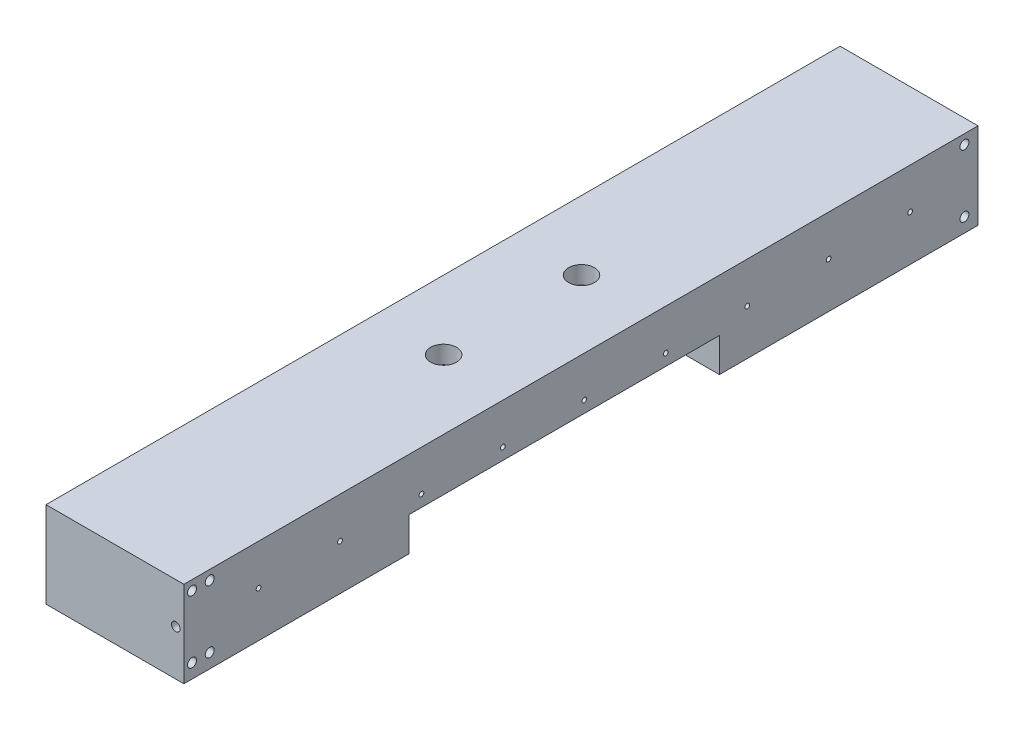
SolidWorks part; units mm, degrees
ref_plane "Front" through (0, 0, 0) normal (0, 0, 1) x (1, 0, 0)
ref_plane "Top" through (0, 0, 0) normal (0, 1, 0) x (1, 0, 0)
ref_plane "Right" through (0, 0, 0) normal (1, 0, 0) x (0, 0, -1)
sketch "Sketch1" plane through (0, 0, 0) normal (0, 0, 1) x (1, 0, 0)
  line L1 (0, 0) -> (101.6, 0)
  line L2 (0, 0) -> (0, 63.5)
  line L3 (0, 63.5) -> (101.6, 63.5)
  line L4 (101.6, 0) -> (101.6, 63.5)
  dimension "D1" = 63.5
  dimension "D2" = 101.6
extrude "Boss-Extrude1" add sketch "Sketch1" along normal blind 585.0001
sketch "Sketch2" plane through (0, 0, 0) normal (-1, 0, 0) x (0, 0, 1)
  line L0 (190.5, 0) -> (190.5, 25)
  line L1 (585.0001, 0) -> (0, 0) construction
  line L2 (190.5, 25) -> (419.1, 25)
  line L3 (419.1, 25) -> (419.1, 0)
  line L4 (419.1, 0) -> (190.5, 0)
  line L5 (0, 63.5) -> (0, 0) construction
  line L6 (393.7, 25) -> (190.5, 25) construction
  dimension "D1" = 190.5
  dimension "D3" = 228.6
extrude "Cut-Extrude1" cut sketch "Sketch2" against normal through all
sketch "Sketch5" plane through (0, 0, 0) normal (-1, 0, 0) x (0, 0, 1)
  arc A0 (6.7, 10.5) -> (13.3, 10.5) centre (10, 10.5) ccw construction
  arc A1 (13.3, 10.5) -> (6.7, 10.5) centre (10, 10.5) ccw construction
  arc A2 (6.7, 56.5) -> (13.3, 56.5) centre (10, 56.5) ccw construction
  arc A3 (13.3, 56.5) -> (6.7, 56.5) centre (10, 56.5) ccw construction
  arc A4 (6.7, 10.5) -> (13.3, 10.5) centre (10, 10.5) ccw
  arc A5 (13.3, 10.5) -> (6.7, 10.5) centre (10, 10.5) ccw
  arc A6 (6.7, 56.5) -> (13.3, 56.5) centre (10, 56.5) ccw
  arc A7 (13.3, 56.5) -> (6.7, 56.5) centre (10, 56.5) ccw
  arc A8 (170, 35.25) -> (170, 31.75) centre (170, 33.5) ccw construction
  arc A9 (170, 31.75) -> (170, 35.25) centre (170, 33.5) ccw construction
  arc A10 (110, 31.75) -> (110, 35.25) centre (110, 33.5) ccw construction
  arc A11 (110, 35.25) -> (110, 31.75) centre (110, 33.5) ccw construction
  arc A12 (50, 31.75) -> (50, 35.25) centre (50, 33.5) ccw construction
  arc A13 (50, 35.25) -> (50, 31.75) centre (50, 33.5) ccw construction
  arc A14 (170, 35.25) -> (170, 31.75) centre (170, 33.5) ccw
  arc A15 (170, 31.75) -> (170, 35.25) centre (170, 33.5) ccw
  arc A16 (110, 31.75) -> (110, 35.25) centre (110, 33.5) ccw
  arc A17 (110, 35.25) -> (110, 31.75) centre (110, 33.5) ccw
  arc A18 (50, 31.75) -> (50, 35.25) centre (50, 33.5) ccw
  arc A19 (50, 35.25) -> (50, 31.75) centre (50, 33.5) ccw
  arc A20 (530, 31.75) -> (530, 35.25) centre (530, 33.5) ccw construction
  arc A21 (530, 35.25) -> (530, 31.75) centre (530, 33.5) ccw construction
  arc A22 (470, 31.75) -> (470, 35.25) centre (470, 33.5) ccw construction
  arc A23 (470, 35.25) -> (470, 31.75) centre (470, 33.5) ccw construction
  arc A24 (410, 31.75) -> (410, 35.25) centre (410, 33.5) ccw construction
  arc A25 (410, 35.25) -> (410, 31.75) centre (410, 33.5) ccw construction
  arc A26 (350, 31.75) -> (350, 35.25) centre (350, 33.5) ccw construction
  arc A27 (350, 35.25) -> (350, 31.75) centre (350, 33.5) ccw construction
  arc A28 (290, 31.75) -> (290, 35.25) centre (290, 33.5) ccw construction
  arc A29 (290, 35.25) -> (290, 31.75) centre (290, 33.5) ccw construction
  arc A30 (230, 31.75) -> (230, 35.25) centre (230, 33.5) ccw construction
  arc A31 (230, 35.25) -> (230, 31.75) centre (230, 33.5) ccw construction
  arc A32 (530, 31.75) -> (530, 35.25) centre (530, 33.5) ccw
  arc A33 (530, 35.25) -> (530, 31.75) centre (530, 33.5) ccw
  arc A34 (470, 31.75) -> (470, 35.25) centre (470, 33.5) ccw
  arc A35 (470, 35.25) -> (470, 31.75) centre (470, 33.5) ccw
  arc A36 (410, 31.75) -> (410, 35.25) centre (410, 33.5) ccw
  arc A37 (410, 35.25) -> (410, 31.75) centre (410, 33.5) ccw
  arc A38 (350, 31.75) -> (350, 35.25) centre (350, 33.5) ccw
  arc A39 (350, 35.25) -> (350, 31.75) centre (350, 33.5) ccw
  arc A40 (290, 31.75) -> (290, 35.25) centre (290, 33.5) ccw
  arc A41 (290, 35.25) -> (290, 31.75) centre (290, 33.5) ccw
  arc A42 (230, 31.75) -> (230, 35.25) centre (230, 33.5) ccw
  arc A43 (230, 35.25) -> (230, 31.75) centre (230, 33.5) ccw
  arc A44 (582.3, 10.5) -> (575.7, 10.5) centre (579, 10.5) ccw construction
  arc A45 (575.7, 10.5) -> (582.3, 10.5) centre (579, 10.5) ccw construction
  arc A46 (562.7, 10.5) -> (569.3, 10.5) centre (566, 10.5) ccw construction
  arc A47 (569.3, 10.5) -> (562.7, 10.5) centre (566, 10.5) ccw construction
  arc A48 (575.7, 56.5) -> (582.3, 56.5) centre (579, 56.5) ccw construction
  arc A49 (582.3, 56.5) -> (575.7, 56.5) centre (579, 56.5) ccw construction
  arc A50 (562.7, 56.5) -> (569.3, 56.5) centre (566, 56.5) ccw construction
  arc A51 (569.3, 56.5) -> (562.7, 56.5) centre (566, 56.5) ccw construction
  arc A52 (582.3, 10.5) -> (575.7, 10.5) centre (579, 10.5) ccw
  arc A53 (575.7, 10.5) -> (582.3, 10.5) centre (579, 10.5) ccw
  arc A54 (562.7, 10.5) -> (569.3, 10.5) centre (566, 10.5) ccw
  arc A55 (569.3, 10.5) -> (562.7, 10.5) centre (566, 10.5) ccw
  arc A56 (575.7, 56.5) -> (582.3, 56.5) centre (579, 56.5) ccw
  arc A57 (582.3, 56.5) -> (575.7, 56.5) centre (579, 56.5) ccw
  arc A58 (562.7, 56.5) -> (569.3, 56.5) centre (566, 56.5) ccw
  arc A59 (569.3, 56.5) -> (562.7, 56.5) centre (566, 56.5) ccw
extrude "Cut-Extrude4" cut sketch "Sketch5" along normal blind 6.35 from surface contours A32 A33 | A34 A35 | A36 A37 | A38 A39 | A40 A41 | A42 A43 | A15 A14 | A16 A17 | A18 A19 starting at face at (101.6, 22.125, 298.65)
extrude "Cut-Extrude5" cut sketch "Sketch5<3>" along normal blind 25.4 from surface contours A54 A55 | A52 A53 | A56 A57 | A58 A59 | A4 A5 | A6 A7 region at (0, 10.5, 10) region at (0, 56.5, 10) region at (0, 10.5, 579) region at (0, 10.5, 566) region at (0, 56.5, 579) region at (0, 56.5, 566) starting at face at (101.6, 33.5, 531.75)
sketch "Sketch5<3>" plane through (0, 0, 0) normal (-1, 0, 0) x (0, 0, 1) same geometry as "Sketch5"
sketch "Sketch6" plane through (0, 25, 0) normal (0, -1, 0) x (1, 0, 0)
  circle A0 centre (50.8, 342.9) radius 4.9344 construction
  circle A1 centre (50.8, 241.3) radius 4.9344 construction
  circle A2 centre (50.8, 342.9) radius 4.9344
  circle A3 centre (50.8, 241.3) radius 4.9344
extrude "Cut-Extrude6" cut sketch "Sketch6" against normal through all
sketch "Sketch7" plane through (0, 0, 0) normal (-1, 0, 0) x (0, 0, 1)
  arc A0 (525.6376, 39.6942) -> (531.1303, 39.6942) centre (528.384, 41.2874) ccw construction
  arc A1 (525.6376, 42.8806) -> (525.6376, 39.6942) centre (528.384, 41.2874) ccw construction
  arc A2 (531.1303, 42.8806) -> (525.6376, 42.8806) centre (528.384, 41.2874) ccw construction
  arc A3 (531.1303, 39.6942) -> (531.1303, 42.8806) centre (528.384, 41.2874) ccw construction
  arc A4 (525.6376, 39.6942) -> (531.1303, 39.6942) centre (528.384, 41.2874) ccw
  arc A5 (525.6376, 42.8806) -> (525.6376, 39.6942) centre (528.384, 41.2874) ccw
  arc A6 (531.1303, 42.8806) -> (525.6376, 42.8806) centre (528.384, 41.2874) ccw
  arc A7 (531.1303, 39.6942) -> (531.1303, 42.8806) centre (528.384, 41.2874) ccw
  arc A8 (53.5485, 42.8806) -> (48.0559, 42.8806) centre (50.8022, 41.2874) ccw construction
  arc A9 (53.5485, 39.6942) -> (53.5485, 42.8806) centre (50.8022, 41.2874) ccw construction
  arc A10 (48.0559, 39.6942) -> (53.5485, 39.6942) centre (50.8022, 41.2874) ccw construction
  arc A11 (48.0559, 42.8806) -> (48.0559, 39.6942) centre (50.8022, 41.2874) ccw construction
  arc A12 (53.5485, 42.8806) -> (48.0559, 42.8806) centre (50.8022, 41.2874) ccw
  arc A13 (53.5485, 39.6942) -> (53.5485, 42.8806) centre (50.8022, 41.2874) ccw
  arc A14 (48.0559, 39.6942) -> (53.5485, 39.6942) centre (50.8022, 41.2874) ccw
  arc A15 (48.0559, 42.8806) -> (48.0559, 39.6942) centre (50.8022, 41.2874) ccw
extrude "Cut-Extrude7" cut sketch "Sketch7" against normal blind 12.7
sketch "Sketch8" plane through (0, 0, 585.0001) normal (0, 0, 1) x (1, 0, 0)
  circle A0 centre (95.65, 33.5) radius 3.175 construction
  circle A1 centre (95.65, 33.5) radius 3.175
extrude "Cut-Extrude8" cut sketch "Sketch8" against normal blind 12.7
sketch "Sketch10" plane through (0, -0.4, 0) normal (0, 1, 0) x (1, 0, 0)
  circle A0 centre (50.8, -342.9) radius 9.525
  circle A1 centre (50.8, -342.9) radius 4.9344 construction
  circle A2 centre (50.8, -241.3) radius 9.525
  circle A3 centre (50.8, -241.3) radius 4.9344 construction
  dimension "D1" = 19.05
extrude "Cut-Extrude10" cut sketch "Sketch10" along normal through all from offset 50.8
